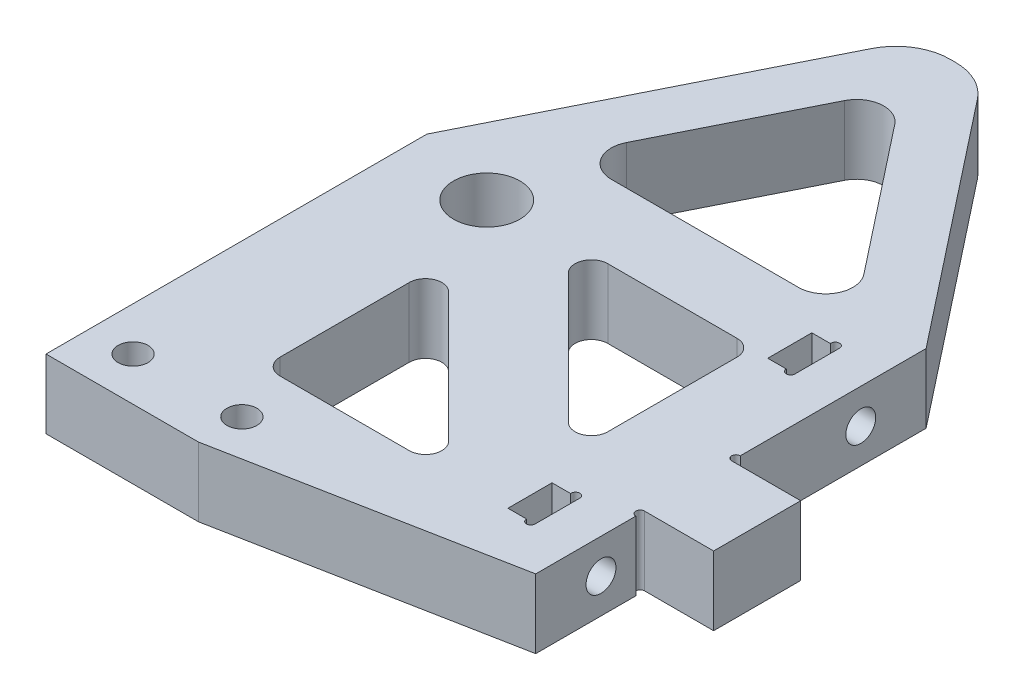
SolidWorks part; units mm, degrees
material "6061 Alloy"
ref_plane "Front Plane" through (0, 0, 0) normal (0, 0, 1) x (1, 0, 0)
ref_plane "Top Plane" through (0, 0, 0) normal (0, 1, 0) x (1, 0, 0)
ref_plane "Right Plane" through (0, 0, 0) normal (1, 0, 0) x (0, 0, -1)
sketch "Sketch1" plane through (0, 0, 0) normal (0, 1, 0) x (1, 0, 0)
  line L1 (-80, 0) -> (-80, 60)
  line L7 (0, 0) -> (-52, -10)
  line L8 (-52, -10) -> (-80, -10)
  line L9 (-80, -10) -> (-80, 0)
  line L10 (-80, 60) -> (-50, 120)
  line L11 (-50, 120) -> (-38, 120)
  line L12 (-38, 120) -> (0, 71.75)
  line L14 (0, 36) -> (12.7, 36)
  line L15 (12.7, 36) -> (12.7, 20)
  line L16 (12.7, 20) -> (0, 20)
  line L18 (0, 18.4) -> (0, 0)
  line L19 (0, 71.75) -> (0, 37.6)
  circle A0 centre (-64, 55) radius 6.1
  circle A3 centre (-72, -2) radius 2.75
  circle A4 centre (-52, -2) radius 2.75
  arc A5 (0, 20) -> (0, 18.4) centre (0, 19.2) ccw
  arc A6 (0, 36) -> (0, 37.6) centre (0, 36.8) cw
  point P23 (12.7, 28)
  dimension "D8" = 12.2
  dimension "D12" = 5.5
  dimension "D16" = 5.5
  dimension "D19" = 0.8
  dimension "D20" = 0.8
  dimension "D1" = 80
  dimension "D2" = 71.75
  dimension "D3" = 60
  dimension "D9" = 16
  dimension "D14" = 8
  dimension "D15" = 20
  dimension "D10" = 10
  dimension "D13" = 8
  dimension "D17" = 55
  dimension "D4" = 60
  dimension "D5" = 30
  dimension "D6" = 12
  dimension "D18" = 12.7
  dimension "D7" = 28
  dimension "D11" = 16
extrude "Boss-Extrude1" add sketch "Sketch1" along normal blind 12.7
fillet "Fillet1" radius 10 2 edges at (-38, 6.35, -120) (-50, 6.35, -120)
sketch "Sketch3" plane through (0, 12.7, 0) normal (0, 1, 0) x (1, 0, 0)
  line L5 (-11.1538, 69.75) -> (-43.4444, 110.7505)
  line L6 (-43.4444, 110.7505) -> (-63.9447, 69.75)
  line L7 (-63.9447, 69.75) -> (-11.1538, 69.75)
  line L8 (-58, 34.7574) -> (-58, 11)
  line L9 (-55, 8) -> (-31.2426, 8)
  line L10 (0, 71.75) -> (-34.9972, 116.1872) construction
  line L11 (-52.7639, 114.4721) -> (-80, 60) construction
  line L12 (-29.1213, 13.1213) -> (-52.8787, 36.8787)
  line L13 (-16, 29.2426) -> (-16, 53)
  line L14 (-19, 56) -> (-42.7574, 56)
  line L15 (-44.8787, 50.8787) -> (-21.1213, 27.1213)
  line L16 (-80, 60) -> (-80, -10) construction
  line L17 (-80, -10) -> (-52, -10) construction
  arc A0 (-16, 53) -> (-19, 56) centre (-19, 53) ccw
  arc A1 (-44.8787, 50.8787) -> (-42.7574, 56) centre (-42.7574, 53) cw
  arc A2 (-16, 29.2426) -> (-21.1213, 27.1213) centre (-19, 29.2426) cw
  arc A3 (-31.2426, 8) -> (-29.1213, 13.1213) centre (-31.2426, 11) ccw
  arc A4 (-55, 8) -> (-58, 11) centre (-55, 11) cw
  arc A5 (-58, 34.7574) -> (-52.8787, 36.8787) centre (-55, 34.7574) cw
  point P21 (-16, 56)
  point P24 (-50, 56)
  point P27 (-16, 22)
  point P30 (-24, 8)
  point P33 (-58, 8)
  point P36 (-58, 42)
  dimension "D14" = 3
  dimension "D1" = 10
  dimension "D2" = 10
  dimension "D3" = 10
  dimension "D4" = 10
  dimension "D5" = 2
  dimension "D6" = 22
  dimension "D7" = 18
  dimension "D8" = 34
  dimension "D9" = 34
  dimension "D10" = 64
  dimension "D11" = 32
  dimension "D12" = 34
  dimension "D13" = 34
extrude "Cut-Extrude1" cut sketch "Sketch3" against normal through all
fillet "Fillet2" radius 5 3 edges at (-43.4444, 6.35, -110.7505) (-11.1538, 6.35, -69.75) (-63.9447, 6.35, -69.75)
sketch "Sketch4" plane through (0, 12.7, 0) normal (0, 1, 0) x (1, 0, 0)
  line L0 (0, 0) -> (0, 18.4) construction
  line L2 (-13, 16) -> (-13, 7.9)
  line L4 (-8, 16.1) -> (-8, 7.9)
  line L5 (-13, 16) -> (-9.5937, 16)
  line L6 (-13, 7.9) -> (-9.6, 7.9)
  line L7 (-13, 55.65) -> (-9.6, 55.65)
  line L8 (-8, 63.85) -> (-8, 55.65)
  line L9 (-13, 63.75) -> (-9.5937, 63.75)
  line L10 (-13, 63.75) -> (-13, 55.65)
  arc A0 (-8, 16.1) -> (-9.5937, 16) centre (-8.8, 16.1) ccw
  arc A1 (-8, 7.9) -> (-9.6, 7.9) centre (-8.8, 7.9) cw
  arc A2 (-8, 55.65) -> (-9.6, 55.65) centre (-8.8, 55.65) cw
  arc A3 (-8, 63.85) -> (-9.5937, 63.75) centre (-8.8, 63.85) ccw
  point P4 (-8, 12)
  point P12 (-8, 59.75)
  dimension "D5" = 0.8
  dimension "D1" = 12
  dimension "D2" = 8
  dimension "D3" = 8.2
  dimension "D4" = 5
  dimension "D7" = 12
  dimension "D6" = 2
extrude "Cut-Extrude2" cut sketch "Sketch4" against normal through all
sketch "Sketch6" plane through (-8, 0, 0) normal (-1, 0, 0) x (0, 0, 1)
  line L0 (-7.9, 0) -> (-7.9, 12.7) construction
  line L1 (-7.9, 12.7) -> (-16.1, 12.7) construction
  line L2 (-55.65, 0) -> (-55.65, 12.7) construction
  circle A0 centre (-12, 6.35) radius 2.75
  circle A1 centre (-59.75, 6.35) radius 2.75
  dimension "D2" = 5.5
  dimension "D5" = 5.5
  dimension "D1" = 4.1
  dimension "D3" = 6.35
  dimension "D4" = 4.1
extrude "Cut-Extrude3" cut sketch "Sketch6" against normal through all
equation "\"DriveMotorLength\"= 90mm"
equation "\"DriveMotorGap\"= 10mm"
equation "\"AluminumThickness\"= 0.5in"
equation "\"ChassisWidth\"= ( \"DriveMotorLength\" + \"AluminumThickness\" ) * 2 + \"DriveMotorGap\""
equation "\"RepeatMagnumHoleWidth\"= 19.05mm"
equation "\"MortiseWidth\"= 16mm"
equation "\"ChassisScrewThruHole\"= 5.5mm"
equation "\"D12@Sketch1\"=\"ChassisScrewThruHole\""
equation "\"D16@Sketch1\"=\"ChassisScrewThruHole\""
equation "\"MortiseSlotWidth\"= 16.2mm"
equation "\"Dogbone\"= 0.8mm"
equation "\"D19@Sketch1\"=\"Dogbone\""
equation "\"D20@Sketch1\"=\"Dogbone\""
equation "\"D5@Sketch4\"=\"Dogbone\""
equation "\"D2@Sketch6\"=\"ChassisScrewThruHole\""
equation "\"D5@Sketch6\"=\"ChassisScrewThruHole\""
equation "\"D11@Sketch1\"=\"MortiseWidth\""
